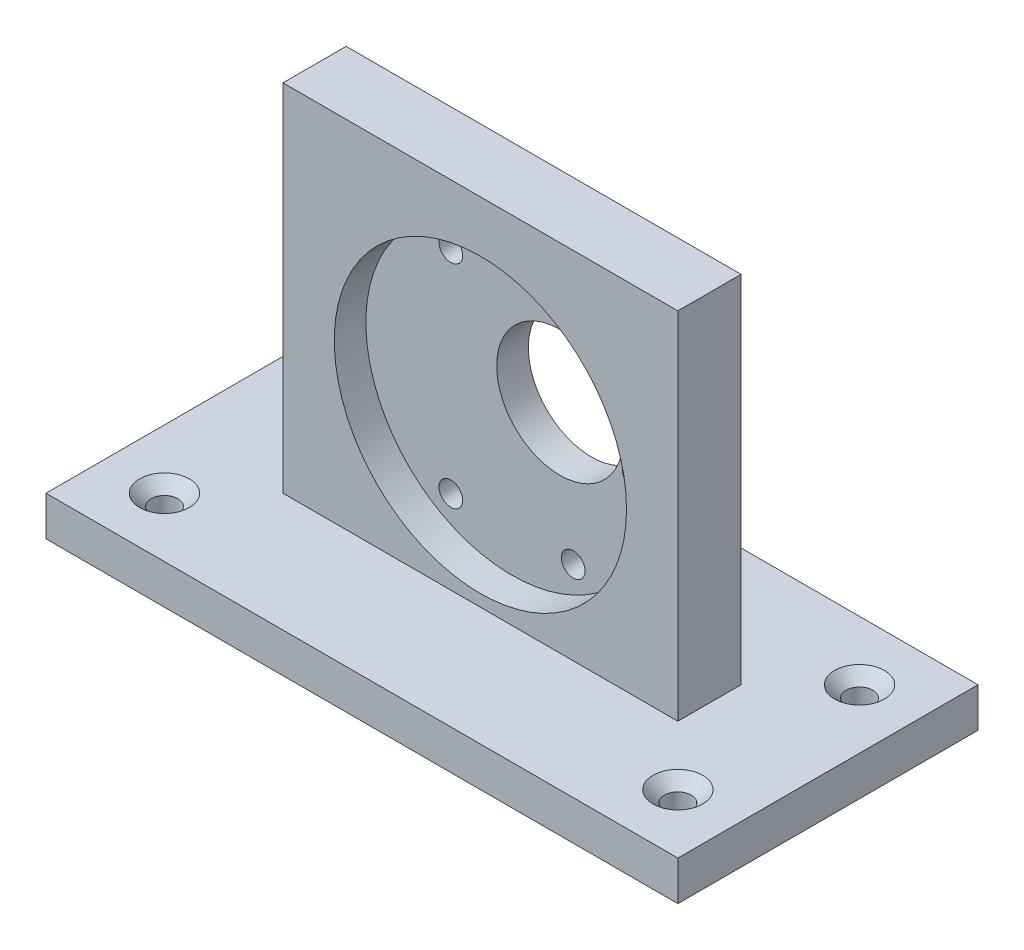
SolidWorks part; units mm, degrees
other "Markup1"
sketch "Sketch5" plane through (25, 50, 8) normal (0.9645, 0.1424, 0.2224) x (0.1697, 0.3107, -0.9352)
ref_plane "Front Plane" through (0, 0, 0) normal (0, 0, 1) x (1, 0, 0)
ref_plane "Top Plane" through (0, 0, 0) normal (0, 1, 0) x (1, 0, 0)
ref_plane "Right Plane" through (0, 0, 0) normal (1, 0, 0) x (0, 0, -1)
sketch "Sketch3" plane through (0, 0, 0) normal (0, 0, 1) x (1, 0, 0)
  line L1 (-25, 50) -> (25, 50)
  line L2 (-25, 50) -> (-25, 0)
  line L3 (-25, 0) -> (25, 0)
  line L4 (25, 50) -> (25, 0)
  line L5 (-7.75, 38.4234) -> (7.75, 38.4234) construction
  line L6 (7.75, 38.4234) -> (15.5, 25) construction
  line L7 (15.5, 25) -> (7.75, 11.5766) construction
  line L8 (7.75, 11.5766) -> (-7.75, 11.5766) construction
  line L9 (-7.75, 11.5766) -> (-15.5, 25) construction
  line L10 (-15.5, 25) -> (-7.75, 38.4234) construction
  line L12 (-20.1843, 13.3466) -> (22.8058, 38.167) construction
  circle A5 centre (-7.75, 38.4234) radius 1.5
  circle A6 centre (7.75, 38.4234) radius 1.5
  circle A8 centre (-7.75, 11.5766) radius 1.5
  circle A9 centre (7.75, 11.5766) radius 1.5
  circle A10 centre (15.5, 25) radius 1.5
  circle A11 centre (6.0622, 28.5) radius 8
  point P4 (0, 0)
  point P27 (-11.625, 18.2883)
  point P28 (11.625, 31.7117)
  dimension "D4" = 25
  dimension "D9" = 16
  dimension "D3" = 3
  dimension "D1" = 50
  dimension "D2" = 50
  dimension "D6" = 120
  dimension "D7" = 120
  dimension "D8" = 15.5
  dimension "D10" = 6.4234
extrude "Boss-Extrude1" add sketch "Sketch3" along normal blind 8 contours L2 L3 L4 L1
extrude "Cut-Extrude2" cut sketch "Sketch3<3>" along normal blind 10 contours A6 | A5 | A8 | A9 | A10 | A11
sketch "Sketch3<3>" plane through (0, 0, 0) normal (0, 0, 1) x (1, 0, 0) same geometry as "Sketch3"
sketch "Sketch4" plane through (0, 0, 8) normal (0, 0, 1) x (1, 0, 0)
  line L0 (-15.5, 25) -> (15.5, 25) construction
  circle A0 centre (0, 25) radius 18.5
  dimension "D1" = 37
extrude "Cut-Extrude3" cut sketch "Sketch4" against normal blind 4 contours A0
sketch "Sketch6" plane through (0, 0, 8) normal (0, 0, 1) x (1, 0, 0)
  line L1 (-40, 5) -> (40, 5)
  line L2 (-40, 5) -> (-40, 0)
  line L3 (-40, 0) -> (40, 0)
  line L4 (40, 5) -> (40, 0)
  point P4 (0, 0)
  dimension "D1" = 80
  dimension "D2" = 5
extrude "Boss-Extrude2" add sketch "Sketch6" against normal blind 23 and the other way blind 15
sketch "Sketch7" plane through (0, 5, 0) normal (0, 1, 0) x (1, 0, 0)
  line L0 (-40, -23) -> (-40, 15) construction
  line L1 (-40, -23) -> (-32.5, -23)
  line L2 (-40, -23) -> (-40, -15.5)
  line L3 (-40, -15.5) -> (-32.5, -15.5)
  line L4 (-32.5, -23) -> (-32.5, -15.5)
  line L5 (-40, -4) -> (40, -4) construction
  line L6 (40, -23) -> (40, 15) construction
  line L7 (0, 15) -> (0, -23) construction
  line L8 (40, 15) -> (-40, 15) construction
  line L9 (40, -23) -> (-40, -23) construction
  point P18 (-32.5, 7.5)
  point P20 (32.5, -15.5)
  point P21 (32.5, 7.5)
  dimension "D1" = 7.5
hole_wizard "CSK for M3 Flat Head Machine Screw1" positions "Sketch8" profile "Sketch9" countersink size "M3" standard "ANSI Metric" end condition through all
sketch "Sketch8" plane through (0, 5, 0) normal (0, 1, 0) x (1, 0, 0)
  point P0 (-32.5, 7.5)
  point P3 (-32.5, -15.5)
  point P6 (32.5, -15.5)
  point P9 (32.5, 7.5)
sketch "Sketch9" plane through (-32.5, 5, -7.5) normal (1, 0, 0) x (0, 0, 1)
  line L0 (0, 0) -> (0, 5)
  line L1 (0, 5) -> (1.7, 5)
  line L2 (1.7, 5) -> (1.7, 1.45)
  line L3 (1.7, 1.45) -> (3.15, 0)
  line L5 (3.15, 0) -> (0, 0)
  line L6 (-1.7, 1.45) -> (-3.15, 0) construction
  line L11 (0, -6.35) -> (0, 107.95) construction
  dimension "Thru Hole Dia." = 3.4
  dimension "Thru Hole Depth" = 5
  dimension "Near C'Sink Dia." = 6.3
  dimension "Near C'Sink Angle" = 90
sketch "Sketch11" plane through (0, 0, 0) normal (0, 0, -1) x (-1, 0, 0)
  line L2 (-6.0622, 28.5) -> (17.9178, 28.5) construction
  circle A0 centre (17.9178, 28.5) radius 5.207
  circle A1 centre (17.9178, 28.5) radius 6.207
  dimension "D2" = 10.414
  dimension "D3" = 12.414
  dimension "D1" = 23.98
extrude "Boss-Extrude3" add sketch "Sketch11" along normal blind 5
